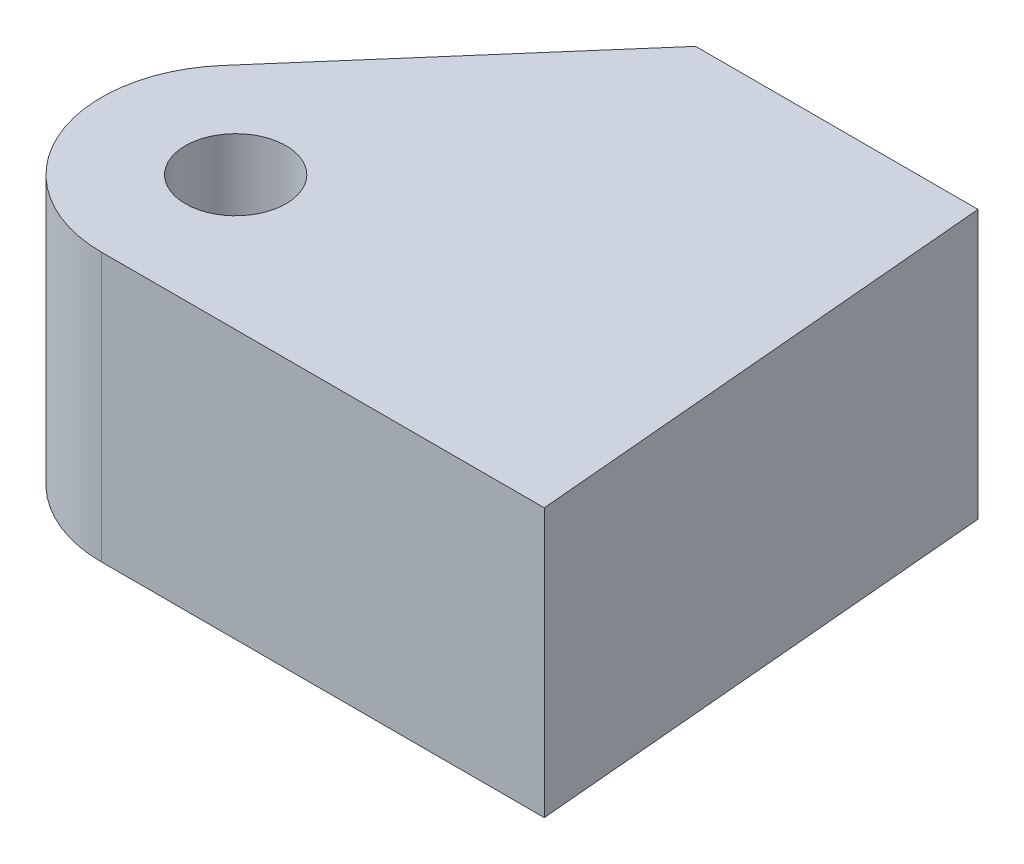
SolidWorks part; units mm, degrees
ref_plane "Front Plane" through (0, 0, 0) normal (0, 0, 1) x (1, 0, 0)
ref_plane "Top Plane" through (0, 0, 0) normal (0, 1, 0) x (1, 0, 0)
ref_plane "Right Plane" through (0, 0, 0) normal (1, 0, 0) x (0, 0, -1)
sketch "Sketch1" plane through (0, 0, 0) normal (0, 1, 0) x (1, 0, 0)
  line L0 (0, 38.6865) -> (0, 0) construction
  line L1 (0, 0) -> (6, 0) construction
  line L2 (6, 0) -> (39, 28.6865) construction
  line L3 (39, 28.6865) -> (72, 0) construction
  line L4 (72, 0) -> (78, 0) construction
  line L5 (78, 0) -> (78, 38.6865) construction
  line L6 (78, 38.6865) -> (0, 38.6865) construction
  line L7 (7.5418, 14.1713) -> (0.9812, 6.6242)
  line L8 (7.5418, 14.1713) -> (15.9602, 14.1713)
  line L9 (4, 0) -> (17.2, 0)
  line L10 (17.5, 15.9916) -> (17.5, 0.8497) construction
  line L11 (17.2, 0) -> (15.9602, 14.1713)
  circle A0 centre (4, 4) radius 1.5
  arc A1 (0.9812, 6.6242) -> (4, 0) centre (4, 4) ccw
  circle A2 centre (39, -0.5) radius 21.5 construction
  dimension "D5" = 3
  dimension "D11" = 4
  dimension "D13" = 43
  dimension "D3" = 98
  dimension "D1" = 6
  dimension "D2" = 78
  dimension "D4" = 10
  dimension "D6" = 4
  dimension "D7" = 4
  dimension "D8" = 13.2
  dimension "D9" = 85
  dimension "D10" = 17.5
  dimension "D12" = 49
  dimension "D14" = 0.5
  dimension "D15" = 10
  dimension "D16" = 95
extrude "Boss-Extrude1" add sketch "Sketch1" along normal blind 8
